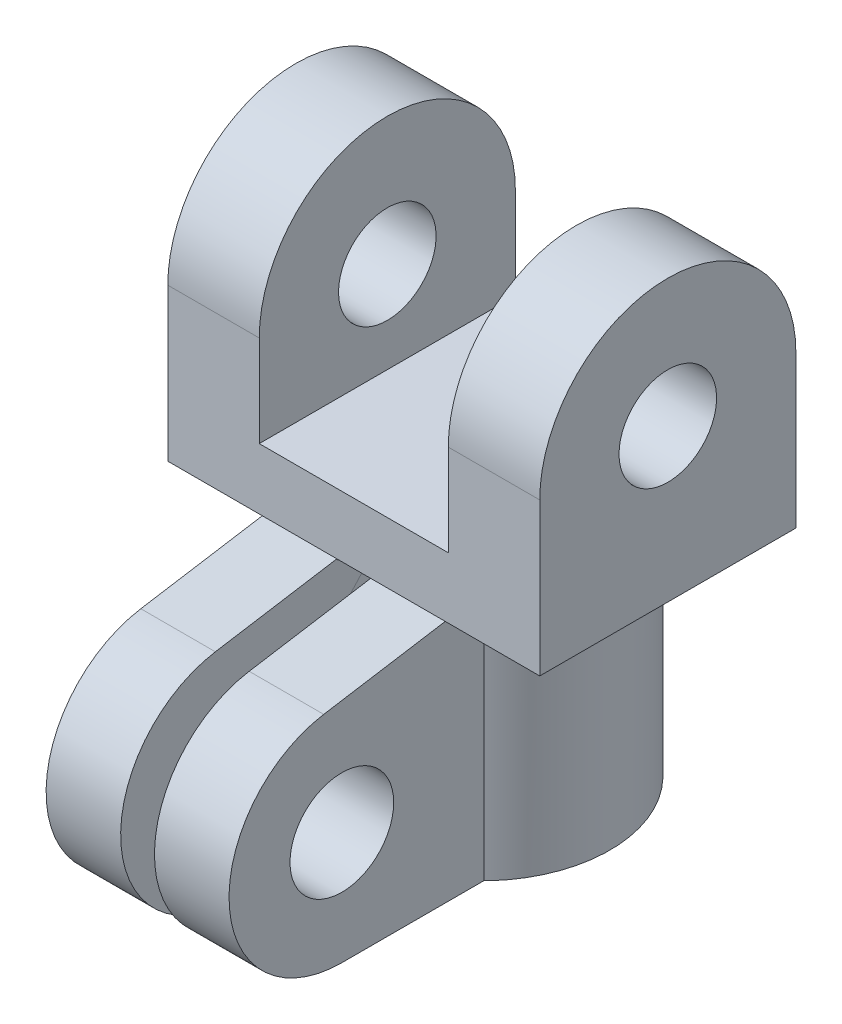
SolidWorks part; units mm, degrees
ref_plane "前视基准面" through (0, 0, 0) normal (0, 0, 1) x (1, 0, 0)
ref_plane "上视基准面" through (0, 0, 0) normal (0, 1, 0) x (1, 0, 0)
ref_plane "右视基准面" through (0, 0, 0) normal (1, 0, 0) x (0, 0, -1)
sketch "草图1" plane through (0, 0, 0) normal (0, 1, 0) x (1, 0, 0)
  circle A0 centre (0, 0) radius 2.7
  circle A1 centre (0, 0) radius 4.2
  dimension "D1" = 5.4
  dimension "D2" = 8.4
extrude "凸台-拉伸1" add sketch "草图1" along normal blind 8
sketch "草图2" plane through (0, 8, 0) normal (0, 1, 0) x (1, 0, 0)
  line L1 (-6.1, -4.2) -> (6.1, -4.2)
  line L2 (-6.1, -4.2) -> (-6.1, 4.2)
  line L3 (-6.1, 4.2) -> (6.1, 4.2)
  line L4 (6.1, -4.2) -> (6.1, 4.2)
  line L5 (-6.1, -4.2) -> (6.1, 4.2) construction
  line L6 (-6.1, 4.2) -> (6.1, -4.2) construction
  circle A0 centre (0, 0) radius 4.2 construction
  point P0 (0, 0)
  dimension "D1" = 12.2
extrude "凸台-拉伸2" add sketch "草图2" along normal blind 2
sketch "草图3" plane through (-6.1, 0, 0) normal (-1, 0, 0) x (0, 0, 1)
  line L3 (0, 20.2944) -> (0, -2.8579) construction
  line L4 (-4.2, 10) -> (4.2, 10)
  line L5 (-4.2, 13) -> (-4.2, 10)
  line L6 (4.2, 13) -> (4.2, 10)
  arc A0 (4.2, 13) -> (-4.2, 13) centre (0, 13) ccw
  circle A1 centre (0, 13) radius 1.6
  dimension "D2" = 8.4
extrude "凸台-拉伸3" add sketch "草图3" against normal blind 3
mirror "镜向1" about plane through (0, 0, 0) normal (1, 0, 0) of "凸台-拉伸2", "凸台-拉伸3"
sketch "草图4" plane through (0, 0, 0) normal (1, 0, 0) x (0, 0, -1)
  line L0 (3.7169, 3.7) -> (-10.9198, 3.7) construction
  line L1 (-4.2, 8) -> (-8.1851, 7.352)
  line L4 (-4.2, 0) -> (4.2, 0) construction
  line L6 (-5.5913, 8.8815) -> (-5.5913, 0.2673) construction
  line L7 (-4.2, 8) -> (0, 8)
  line L8 (-4.2, 8) -> (4.2, 8) construction
  line L12 (-7.5913, 0) -> (0, 0)
  line L13 (0, 0) -> (0, 8)
  circle A2 centre (-7.5913, 3.7) radius 1.7
  arc A4 (-8.1851, 7.352) -> (-7.5913, 0) centre (-7.5913, 3.7) ccw
  dimension "D1" = 2
  dimension "D3" = 7.4
  dimension "D2" = 3.4
  dimension "D4" = 3.7
extrude "凸台-拉伸4" add sketch "草图4" along normal blind 3 and the other way blind 3 separate body
sketch "草图5" plane through (0, 0, 0) normal (0, -1, 0) x (1, 0, 0)
  circle A0 centre (0, 0) radius 2.7 construction
  circle A1 centre (0, 0) radius 2.7
extrude "切除-拉伸1" cut sketch "草图5" against normal blind 6
sketch "草图6" plane through (0, 0, 0) normal (0, 0, 1) x (1, 0, 0)
  line L0 (0, -1.3797) -> (0, 16.8476) construction
  line L8 (-6.1, 8) -> (0, 8) construction
  line L9 (-0.5547, 8) -> (-0.5547, 0)
  line L11 (0.5547, 8) -> (0.5547, 0)
  line L12 (-0.5547, 8) -> (0.5547, 8)
  line L13 (-0.5547, 0) -> (0.5547, 0)
  point P11 (0, 0)
  point P12 (0, 8)
  point P13 (0, 0)
  point P14 (0, 8)
extrude "切除-拉伸2" cut sketch "草图6" along normal through all
sketch "草图7" plane through (0, 0, 0) normal (0, -1, 0) x (1, 0, 0)
  circle A1 centre (0, 0) radius 2.7
extrude "切除-拉伸3" cut sketch "草图7" against normal up to surface (8 mm away) up to face at (0, 8, -0.065)
fillet "圆角1" radius 0.5 3 edges at (4.1908, 8, -0.278) (0, 8, -2.7) (-4.1908, 8, -0.278)
fillet "圆角2" radius 0.5 4 edges at (0.5547, 3.75, 2.6424) (-0.5547, 7.8071, 2.5346) (0.5547, 7.885, 2.4572) (-0.5547, 3.75, 2.6424)
sketch "草图9" plane through (0, 0, 0) normal (0, 0, 1) x (1, 0, 0)
  line L0 (-5.7678, 8.1011) -> (-4, 6.3334)
  line L4 (-6.1, 8) -> (-2.1095, 8) construction
  line L5 (-5.7678, 8.1011) -> (-4, 8.1011)
  line L6 (-4, 8.1011) -> (-4, 6.3334)
  line L7 (-4.2, 7.5) -> (-4.2, 0) construction
  dimension "D1" = 45
  dimension "D2" = 2.5
  dimension "D3" = 0.2
extrude "凸台-拉伸5" add sketch "草图9" along normal mid plane 1
mirror "镜向2" about plane through (0, 0, 0) normal (1, 0, 0) of "凸台-拉伸5"
